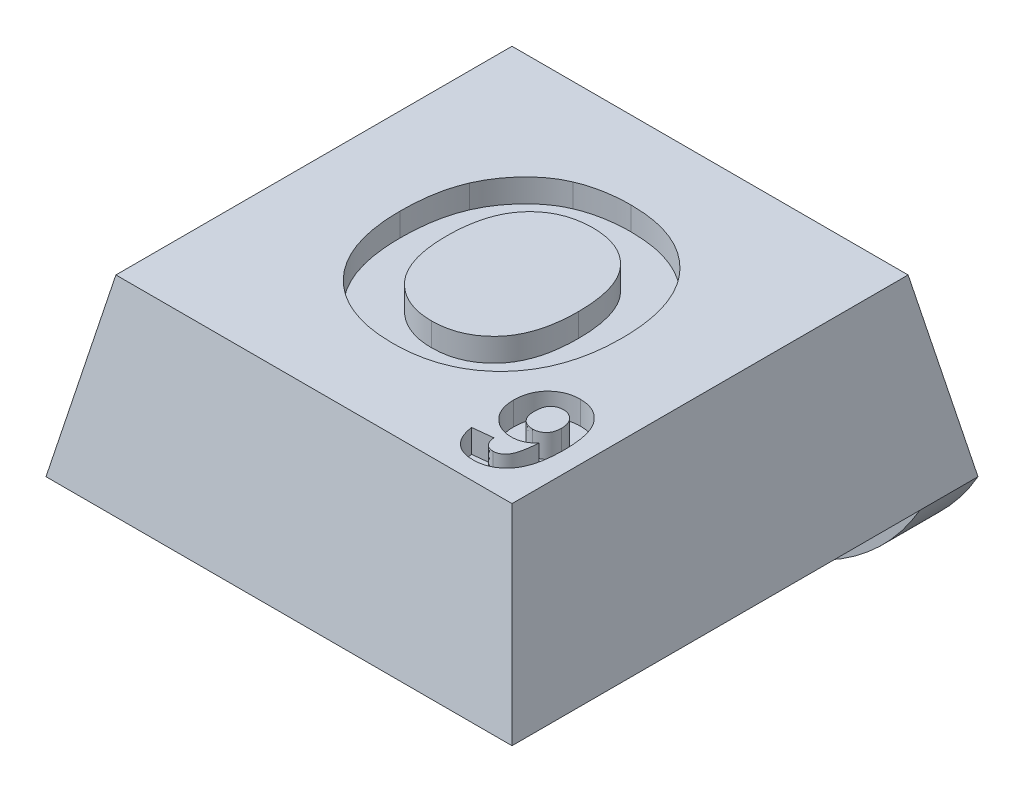
SolidWorks part; units mm, degrees
ref_plane "Front Plane" through (0, 0, 0) normal (0, 0, 1) x (1, 0, 0)
ref_plane "Top Plane" through (0, 0, 0) normal (0, 1, 0) x (1, 0, 0)
ref_plane "Right Plane" through (0, 0, 0) normal (1, 0, 0) x (0, 0, -1)
sketch "Sketch1" plane through (0, 0, 0) normal (0, 1, 0) x (1, 0, 0)
  line L1 (0, 0) -> (8, 0)
  line L2 (0, 0) -> (0, 8)
  line L3 (0, 8) -> (8, 8)
  line L4 (8, 0) -> (8, 8)
  dimension "D1" = 8
  dimension "D2" = 8
extrude "Boss-Extrude1" add sketch "Sketch1" along normal blind 3
sketch "Sketch2" plane through (0, 0, 0) normal (0, 0, 1) x (1, 0, 0)
  line L0 (0, 0) -> (0.6, 3)
  line L1 (0, 3) -> (8, 3) construction
  line L2 (0.6, 3) -> (0, 3)
  line L3 (0, 3) -> (0, 0)
  line L4 (8, 0) -> (7.4, 3)
  line L5 (7.4, 3) -> (8, 3)
  line L6 (8, 3) -> (8, 0)
  dimension "D1" = 0.6
  dimension "D2" = 0.6
extrude "Cut-Extrude1" cut sketch "Sketch2" against normal through all both and the other way through all
sketch "Sketch3" plane through (0, 0, 0) normal (1, 0, 0) x (0, 0, -1)
  line L0 (0, 0) -> (0.6, 3)
  line L1 (8, 3) -> (0, 3) construction
  line L2 (0.6, 3) -> (0, 3)
  line L3 (0, 3) -> (0, 0)
  line L4 (8, 3) -> (7.4, 3)
  line L5 (7.4, 3) -> (8, 0)
  line L6 (8, 3) -> (8, 0)
  dimension "D1" = 0.6
  dimension "D2" = 0.6
extrude "Cut-Extrude2" cut sketch "Sketch3" along normal blind 11
sketch "Sketch4" plane through (0, 0, 0) normal (0, -1, 0) x (1, 0, 0)
  line L0 (8, 0) -> (8, -8) construction
  line L3 (0, 0) -> (8, 0) construction
  circle A0 centre (4, -3.75) radius 1.8
  dimension "D1" = 3.6
  dimension "D2" = 4
  dimension "D3" = 3.75
extrude "Cut-Extrude3" cut sketch "Sketch4" against normal blind 0.8
sketch "Sketch5" plane through (0, 0, 0) normal (0, -1, 0) x (1, 0, 0)
  line L0 (8, 0) -> (8, -8) construction
  line L1 (0, -8) -> (8, -8)
  line L2 (0, -8) -> (0, -7)
  line L3 (0, -7) -> (8, -7)
  line L4 (8, -8) -> (8, -7)
  dimension "D1" = 1
extrude "Boss-Extrude2" add sketch "Sketch5" along normal blind 2
fillet "Fillet1" radius 4 2 edges at (8, -2, -7.5) (0, -2, -7.5)
sketch "Sketch6" plane through (0, 3, 0) normal (0, 1, 0) x (1, 0, 0)
  text T0 "O" font "Arial" height 4
extrude "Cut-Extrude4" cut sketch "Sketch6" against normal blind 0.4
sketch "Sketch7" plane through (0, 3, 0) normal (0, 1, 0) x (1, 0, 0)
  text T0 "9" font "Arial" height 1.8
extrude "Cut-Extrude5" cut sketch "Sketch7" against normal blind 0.4
